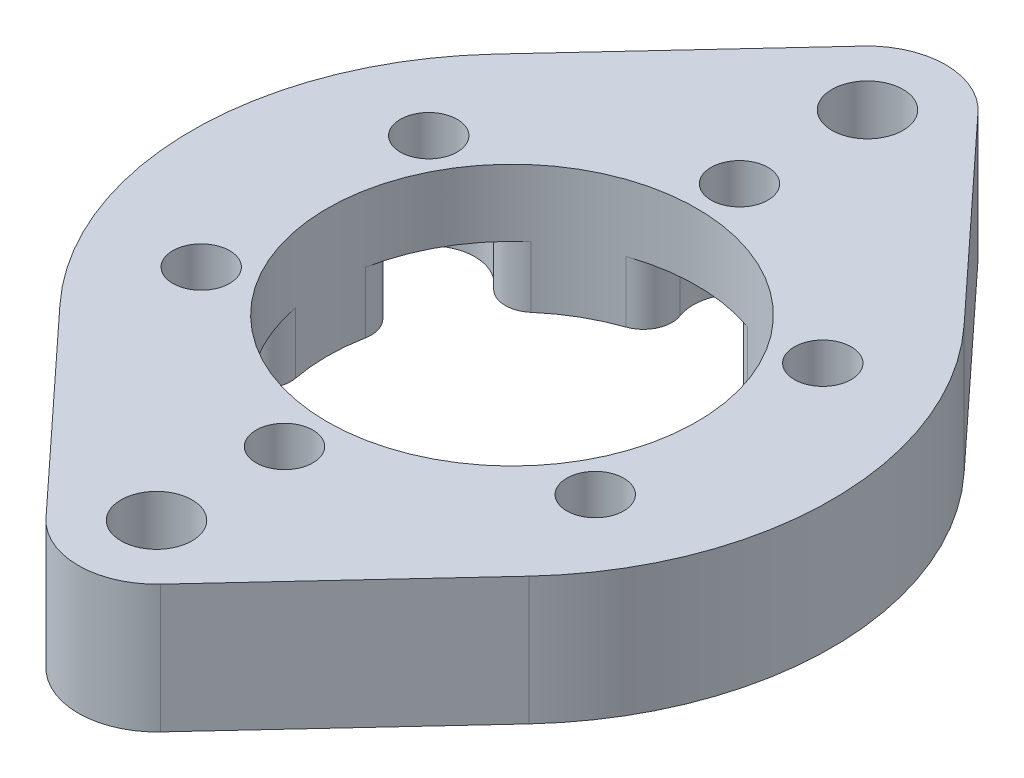
SolidWorks part; units mm, degrees
ref_plane "Front Plane" through (0, 0, 0) normal (0, 0, 1) x (1, 0, 0)
ref_plane "Top Plane" through (0, 0, 0) normal (0, 1, 0) x (1, 0, 0)
ref_plane "Right Plane" through (0, 0, 0) normal (1, 0, 0) x (0, 0, -1)
ref_axis "Axis1" through (0, -54.0054, 0) along (0, 1, 0)
sketch "Sketch1" plane through (0, 0, 0) normal (0, 1, 0) x (1, 0, 0)
  line L0 (0, 13) -> (0, 19) construction
  line L1 (-4.0327, 28.74) -> (-16.4973, 15.3)
  line L3 (-13, 0) -> (13, 0) construction
  line L5 (-4.0327, -28.74) -> (-16.4973, -15.3)
  line L8 (4.0327, 28.74) -> (16.4973, 15.3)
  line L9 (4.0327, -28.74) -> (16.4973, -15.3)
  circle A0 centre (0, 0) radius 13
  circle A1 centre (0, 0) radius 19 construction
  circle A2 centre (0, 16) radius 2
  circle A3 centre (13.8564, 8) radius 2
  circle A4 centre (13.8564, -8) radius 2
  circle A5 centre (0, -16) radius 2
  circle A6 centre (-13.8564, -8) radius 2
  circle A7 centre (-13.8564, 8) radius 2
  circle A8 centre (0, 0) radius 25 construction
  circle A9 centre (0, 25) radius 2.5
  circle A10 centre (0, -25) radius 2.5
  arc A11 (4.0327, 28.74) -> (-4.0327, 28.74) centre (0, 25) ccw
  arc A13 (4.0327, -28.74) -> (-4.0327, -28.74) centre (0, -25) cw
  arc A14 (-16.4973, 15.3) -> (-16.4973, -15.3) centre (0, 0) ccw
  arc A15 (16.4973, -15.3) -> (16.4973, 15.3) centre (0, 0) ccw
  point P21 (0, 0)
  point P27 (0, 0)
  dimension "D1" = 38
  dimension "D2" = 26
  dimension "D3" = 4
  dimension "D5" = 50
  dimension "D6" = 5
  dimension "D8" = 22.5
  dimension "D9" = 3
  dimension "D4" = 6
  dimension "D7" = 2
extrude "Boss-Extrude1" add sketch "Sketch1" along normal blind 9
sketch "Sketch2" plane through (0, 9, 0) normal (0, 1, 0) x (1, 0, 0)
  circle A0 centre (0, 0) radius 19 construction
  circle A1 centre (0, 0) radius 19
extrude "Cut-Extrude1" [suppressed] cut sketch "Sketch2" against normal blind 3.175
ref_plane "Plane1" through (0, 4.3, 0) normal (0, 1, 0) x (1, 0, 0)
sketch "Sketch3" plane through (0, 0, 0) normal (0, -1, 0) x (1, 0, 0)
  circle A0 centre (0, -16) radius 3.25
  circle A1 centre (-13.8564, -8) radius 3.25
  circle A2 centre (-13.8564, 8) radius 3.25
  circle A3 centre (0, 16) radius 3.25
  circle A4 centre (13.8564, 8) radius 3.25
  circle A5 centre (13.8564, -8) radius 3.25
  point P16 (0, 0)
  dimension "D2" = 6.5
  dimension "D1" = 6
extrude "Cut-Extrude2" cut sketch "Sketch3" against normal up to surface (4.3 mm away) up to plane "Plane1"
fillet "Fillet1" radius 2 12 edges at (1.1257, 2.15, -12.9512) (-1.1257, 2.15, -12.9512) (-10.6532, 2.15, -7.4505) (-11.7789, 2.15, -5.5007) (-11.7789, 2.15, 5.5007) (-10.6532, 2.15, 7.4505) (-1.1257, 2.15, 12.9512) (1.1257, 2.15, 12.9512) (10.6532, 2.15, 7.4505) (11.7789, 2.15, 5.5007) (10.6532, 2.15, -7.4505) (11.7789, 2.15, -5.5007)
